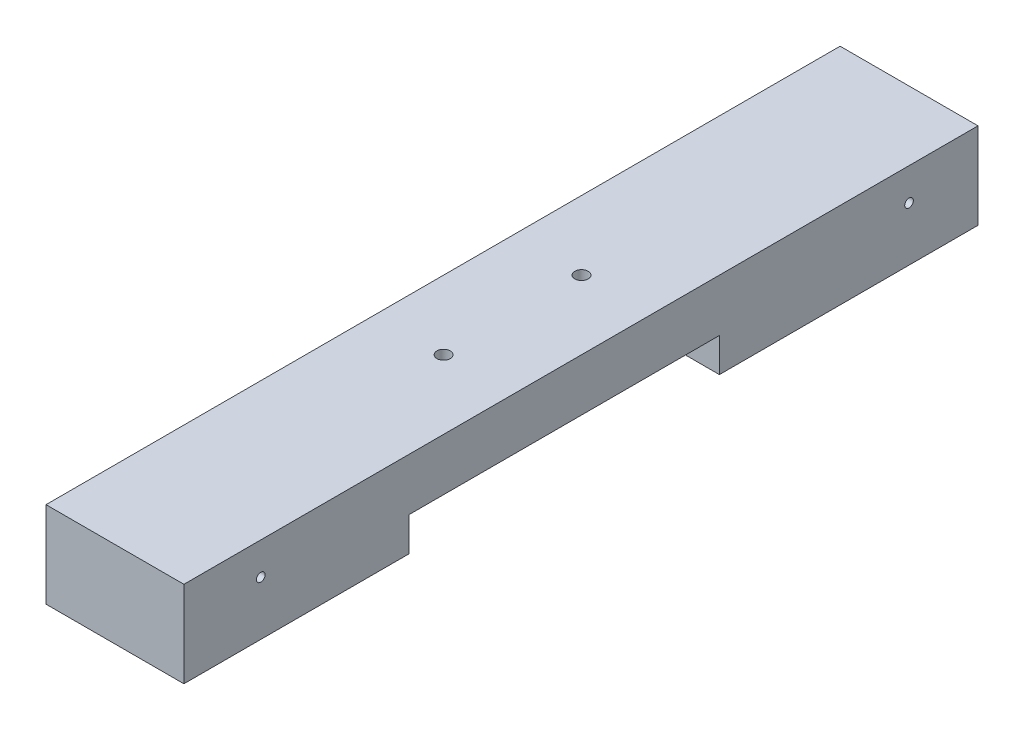
SolidWorks part; units mm, degrees
material "McMaster 6061-T6"
ref_plane "Front" through (0, 0, 0) normal (0, 0, 1) x (1, 0, 0)
ref_plane "Top" through (0, 0, 0) normal (0, 1, 0) x (1, 0, 0)
ref_plane "Right" through (0, 0, 0) normal (1, 0, 0) x (0, 0, -1)
sketch "Sketch1" plane through (0, 0, 0) normal (0, 0, 1) x (1, 0, 0)
  line L1 (0, 0) -> (101.6, 0)
  line L2 (0, 0) -> (0, 63.5)
  line L3 (0, 63.5) -> (101.6, 63.5)
  line L4 (101.6, 0) -> (101.6, 63.5)
  dimension "D1" = 63.5
  dimension "D2" = 101.6
extrude "Boss-Extrude1" add sketch "Sketch1" along normal blind 585.0001
sketch "Sketch2" plane through (0, 0, 0) normal (-1, 0, 0) x (0, 0, 1)
  line L0 (190.5, 0) -> (190.5, 25)
  line L1 (585.0001, 0) -> (0, 0) construction
  line L2 (190.5, 25) -> (419.1, 25)
  line L3 (419.1, 25) -> (419.1, 0)
  line L4 (419.1, 0) -> (190.5, 0)
  line L5 (0, 63.5) -> (0, 0) construction
  point P8 (190.5, 40.7799)
  point P11 (419.1, 57.6493)
  dimension "D1" = 190.5
  dimension "D3" = 228.6
extrude "Cut-Extrude1" cut sketch "Sketch2" against normal through all
sketch "Sketch5" plane through (0, 0, 0) normal (-1, 0, 0) x (0, 0, 1)
  arc A0 (6.7, 6.6) -> (13.3, 6.6) centre (10, 6.6) ccw construction
  arc A1 (13.3, 6.6) -> (6.7, 6.6) centre (10, 6.6) ccw construction
  arc A2 (6.7, 52.6) -> (13.3, 52.6) centre (10, 52.6) ccw construction
  arc A3 (13.3, 52.6) -> (6.7, 52.6) centre (10, 52.6) ccw construction
  arc A4 (6.7, 6.6) -> (13.3, 6.6) centre (10, 6.6) ccw
  arc A5 (13.3, 6.6) -> (6.7, 6.6) centre (10, 6.6) ccw
  arc A6 (6.7, 52.6) -> (13.3, 52.6) centre (10, 52.6) ccw
  arc A7 (13.3, 52.6) -> (6.7, 52.6) centre (10, 52.6) ccw
  arc A8 (170, 31.35) -> (170, 27.85) centre (170, 29.6) ccw construction
  arc A9 (170, 27.85) -> (170, 31.35) centre (170, 29.6) ccw construction
  arc A10 (110, 27.85) -> (110, 31.35) centre (110, 29.6) ccw construction
  arc A11 (110, 31.35) -> (110, 27.85) centre (110, 29.6) ccw construction
  arc A12 (50, 27.85) -> (50, 31.35) centre (50, 29.6) ccw construction
  arc A13 (50, 31.35) -> (50, 27.85) centre (50, 29.6) ccw construction
  arc A14 (170, 31.35) -> (170, 27.85) centre (170, 29.6) ccw
  arc A15 (170, 27.85) -> (170, 31.35) centre (170, 29.6) ccw
  arc A16 (110, 27.85) -> (110, 31.35) centre (110, 29.6) ccw
  arc A17 (110, 31.35) -> (110, 27.85) centre (110, 29.6) ccw
  arc A18 (50, 27.85) -> (50, 31.35) centre (50, 29.6) ccw
  arc A19 (50, 31.35) -> (50, 27.85) centre (50, 29.6) ccw
  arc A20 (530, 27.85) -> (530, 31.35) centre (530, 29.6) ccw construction
  arc A21 (530, 31.35) -> (530, 27.85) centre (530, 29.6) ccw construction
  arc A22 (470, 27.85) -> (470, 31.35) centre (470, 29.6) ccw construction
  arc A23 (470, 31.35) -> (470, 27.85) centre (470, 29.6) ccw construction
  arc A24 (410, 27.85) -> (410, 31.35) centre (410, 29.6) ccw construction
  arc A25 (410, 31.35) -> (410, 27.85) centre (410, 29.6) ccw construction
  arc A26 (350, 27.85) -> (350, 31.35) centre (350, 29.6) ccw construction
  arc A27 (350, 31.35) -> (350, 27.85) centre (350, 29.6) ccw construction
  arc A28 (290, 27.85) -> (290, 31.35) centre (290, 29.6) ccw construction
  arc A29 (290, 31.35) -> (290, 27.85) centre (290, 29.6) ccw construction
  arc A30 (230, 27.85) -> (230, 31.35) centre (230, 29.6) ccw construction
  arc A31 (230, 31.35) -> (230, 27.85) centre (230, 29.6) ccw construction
  arc A32 (530, 27.85) -> (530, 31.35) centre (530, 29.6) ccw
  arc A33 (530, 31.35) -> (530, 27.85) centre (530, 29.6) ccw
  arc A34 (470, 27.85) -> (470, 31.35) centre (470, 29.6) ccw
  arc A35 (470, 31.35) -> (470, 27.85) centre (470, 29.6) ccw
  arc A36 (410, 27.85) -> (410, 31.35) centre (410, 29.6) ccw
  arc A37 (410, 31.35) -> (410, 27.85) centre (410, 29.6) ccw
  arc A38 (350, 27.85) -> (350, 31.35) centre (350, 29.6) ccw
  arc A39 (350, 31.35) -> (350, 27.85) centre (350, 29.6) ccw
  arc A40 (290, 27.85) -> (290, 31.35) centre (290, 29.6) ccw
  arc A41 (290, 31.35) -> (290, 27.85) centre (290, 29.6) ccw
  arc A42 (230, 27.85) -> (230, 31.35) centre (230, 29.6) ccw
  arc A43 (230, 31.35) -> (230, 27.85) centre (230, 29.6) ccw
  arc A44 (582.3, 6.6) -> (575.7, 6.6) centre (579, 6.6) ccw construction
  arc A45 (575.7, 6.6) -> (582.3, 6.6) centre (579, 6.6) ccw construction
  arc A46 (562.7, 6.6) -> (569.3, 6.6) centre (566, 6.6) ccw construction
  arc A47 (569.3, 6.6) -> (562.7, 6.6) centre (566, 6.6) ccw construction
  arc A48 (575.7, 52.6) -> (582.3, 52.6) centre (579, 52.6) ccw construction
  arc A49 (582.3, 52.6) -> (575.7, 52.6) centre (579, 52.6) ccw construction
  arc A50 (562.7, 52.6) -> (569.3, 52.6) centre (566, 52.6) ccw construction
  arc A51 (569.3, 52.6) -> (562.7, 52.6) centre (566, 52.6) ccw construction
  arc A52 (582.3, 6.6) -> (575.7, 6.6) centre (579, 6.6) ccw
  arc A53 (575.7, 6.6) -> (582.3, 6.6) centre (579, 6.6) ccw
  arc A54 (562.7, 6.6) -> (569.3, 6.6) centre (566, 6.6) ccw
  arc A55 (569.3, 6.6) -> (562.7, 6.6) centre (566, 6.6) ccw
  arc A56 (575.7, 52.6) -> (582.3, 52.6) centre (579, 52.6) ccw
  arc A57 (582.3, 52.6) -> (575.7, 52.6) centre (579, 52.6) ccw
  arc A58 (562.7, 52.6) -> (569.3, 52.6) centre (566, 52.6) ccw
  arc A59 (569.3, 52.6) -> (562.7, 52.6) centre (566, 52.6) ccw
extrude "Cut-Extrude4" cut sketch "Sketch5" against normal blind 6.35 from surface contours A32 A33 | A34 A35 | A36 A37 | A38 A39 | A40 A41 | A42 A43 | A15 A14 | A16 A17 | A18 A19 starting at face at (0, 22.125, 298.65)
extrude "Cut-Extrude5" cut sketch "Sketch5<3>" against normal blind 25.4 from surface contours A54 A55 | A52 A53 | A56 A57 | A58 A59 | A4 A5 | A6 A7 region at (0, 6.6, 10) region at (0, 52.6, 10) region at (0, 6.6, 579) region at (0, 6.6, 566) region at (0, 52.6, 579) region at (0, 52.6, 566) starting at face at (0, 29.6, 528.25)
sketch "Sketch5<3>" plane through (0, 0, 0) normal (-1, 0, 0) x (0, 0, 1) same geometry as "Sketch5"
sketch "Sketch6" plane through (0, 25, 0) normal (0, -1, 0) x (1, 0, 0)
  circle A0 centre (50.8, 342.9) radius 4.9344 construction
  circle A1 centre (50.8, 241.3) radius 4.9344 construction
  circle A2 centre (50.8, 342.9) radius 4.9344
  circle A3 centre (50.8, 241.3) radius 4.9344
extrude "Cut-Extrude6" cut sketch "Sketch6" against normal through all
sketch "Sketch7" plane through (101.6, 0, 0) normal (1, 0, 0) x (0, 0, -1)
  arc A0 (-53.5485, 38.1067) -> (-48.0559, 38.1067) centre (-50.8022, 39.6999) ccw construction
  arc A1 (-53.5485, 41.2931) -> (-53.5485, 38.1067) centre (-50.8022, 39.6999) ccw construction
  arc A2 (-48.0559, 41.2931) -> (-53.5485, 41.2931) centre (-50.8022, 39.6999) ccw construction
  arc A3 (-48.0559, 38.1067) -> (-48.0559, 41.2931) centre (-50.8022, 39.6999) ccw construction
  arc A4 (-53.5485, 38.1067) -> (-48.0559, 38.1067) centre (-50.8022, 39.6999) ccw
  arc A5 (-53.5485, 41.2931) -> (-53.5485, 38.1067) centre (-50.8022, 39.6999) ccw
  arc A6 (-48.0559, 41.2931) -> (-53.5485, 41.2931) centre (-50.8022, 39.6999) ccw
  arc A7 (-48.0559, 38.1067) -> (-48.0559, 41.2931) centre (-50.8022, 39.6999) ccw
  arc A8 (-525.6376, 38.1067) -> (-525.6376, 41.2931) centre (-528.384, 39.6999) ccw construction
  arc A9 (-531.1303, 38.1067) -> (-525.6376, 38.1067) centre (-528.384, 39.6999) ccw construction
  arc A10 (-531.1303, 41.2931) -> (-531.1303, 38.1067) centre (-528.384, 39.6999) ccw construction
  arc A11 (-525.6376, 41.2931) -> (-531.1303, 41.2931) centre (-528.384, 39.6999) ccw construction
  arc A12 (-525.6376, 38.1067) -> (-525.6376, 41.2931) centre (-528.384, 39.6999) ccw
  arc A13 (-531.1303, 38.1067) -> (-525.6376, 38.1067) centre (-528.384, 39.6999) ccw
  arc A14 (-531.1303, 41.2931) -> (-531.1303, 38.1067) centre (-528.384, 39.6999) ccw
  arc A15 (-525.6376, 41.2931) -> (-531.1303, 41.2931) centre (-528.384, 39.6999) ccw
extrude "Cut-Extrude7" cut sketch "Sketch7" against normal blind 6.35
